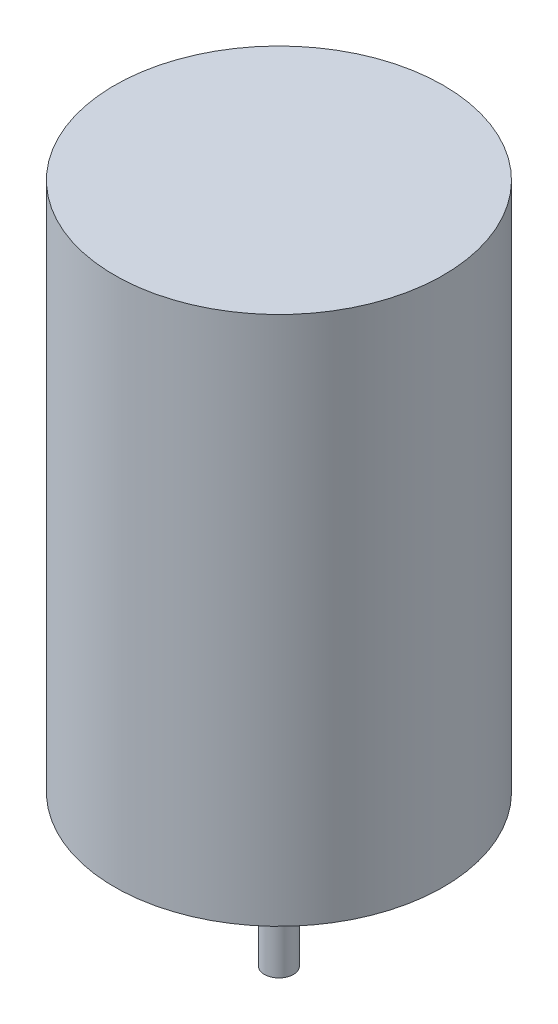
SolidWorks part; units mm, degrees
ref_plane "Front Plane" through (0, 0, 0) normal (0, 0, 1) x (1, 0, 0)
ref_plane "Top Plane" through (0, 0, 0) normal (0, 1, 0) x (1, 0, 0)
ref_plane "Right Plane" through (0, 0, 0) normal (1, 0, 0) x (0, 0, -1)
sketch "Sketch1" plane through (0, 0, 0) normal (0, 1, 0) x (1, 0, 0)
  circle A0 centre (0, 0) radius 18
  dimension "D1" = 36
extrude "Boss-Extrude1" add sketch "Sketch1" along normal blind 58
sketch "Sketch2" plane through (0, 0, 0) normal (0, -1, 0) x (1, 0, 0)
  circle A0 centre (0, 0) radius 1.5875
  dimension "D1" = 3.175
extrude "Boss-Extrude2" add sketch "Sketch2" along normal blind 16.5
sketch "Sketch3" plane through (0, 0, 0) normal (0, -1, 0) x (-1, 0, 0)
  line L0 (-12.5, 0) -> (12.5, 0) construction
  circle A0 centre (0, 0) radius 12.5 construction
  circle A1 centre (0, 0) radius 6.5
  circle A2 centre (-12.5, 0) radius 1.5
  circle A5 centre (12.5, 0) radius 1.5
  circle M4 centre (0, 0) radius 1.5875
  dimension "D1" = 25
  dimension "D2" = 13
  dimension "D4" = 3
  dimension "D5" = 3
extrude "Cut-Extrude1" cut sketch "Sketch3" against normal blind 5 contours A2 | A5 region at (12.5, 0, 0) region at (-12.5, 0, 0)
extrude "Boss-Extrude3" add sketch "Sketch3<3>" along normal blind 4.5 contours A1 M4 region at (6.3162, 0, 0)
sketch "Sketch3<3>" plane through (0, 0, 0) normal (0, -1, 0) x (-1, 0, 0) same geometry as "Sketch3"
